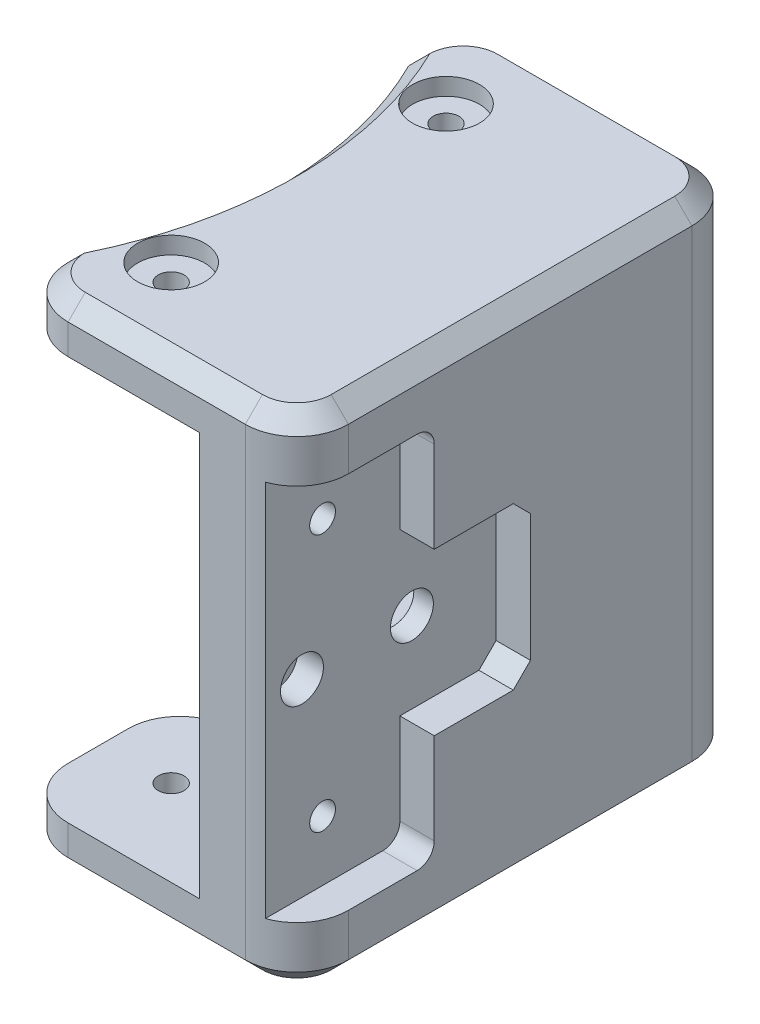
SolidWorks part; units mm, degrees
ref_plane "Спереди" through (0, 0, 0) normal (0, 0, 1) x (1, 0, 0)
ref_plane "Сверху" through (0, 0, 0) normal (0, 1, 0) x (1, 0, 0)
ref_plane "Справа" through (0, 0, 0) normal (1, 0, 0) x (0, 0, -1)
sketch "Эскиз1" plane through (0, 0, 0) normal (0, 1, 0) x (1, 0, 0)
  line L0 (0, 0) -> (25, 0) construction
  line L1 (19.6854, 13) -> (36, 13)
  line L2 (19.6854, 13) -> (19.6854, -13)
  line L3 (19.6854, -13) -> (36, -13)
  line L4 (36, 13) -> (36, -13)
  line L5 (19.6854, 13) -> (36, -13) construction
  line L6 (19.6854, -13) -> (36, 13) construction
  line L7 (23.6854, 8) -> (23.6854, -8) construction
  circle A0 centre (0, 0) radius 25 construction
  circle A1 centre (23.6854, -8) radius 0.75
  circle A2 centre (23.6854, 8) radius 0.75
  point P0 (27.8427, 0)
  dimension "D2" = 50
  dimension "D6" = 1.5
  dimension "D7" = 1.5
  dimension "D1" = 36
  dimension "D3" = 26
  dimension "D4" = 16
  dimension "D5" = 4
extrude "Бобышка-Вытянуть1" add sketch "Эскиз1" along normal mid plane 29
sketch "Эскиз2" plane through (0, 0, 0) normal (0, 1, 0) x (1, 0, 0)
  circle A0 centre (0, 0) radius 33
  dimension "D1" = 66
extrude "Вырез-Вытянуть1" cut sketch "Эскиз2" against normal mid plane 23.5
sketch "Эскиз3" plane through (36, 0, 0) normal (1, 0, 0) x (0, 0, -1)
  line L0 (-13, 11) -> (-5, 11)
  line L1 (-13, 14.5) -> (-13, -14.5) construction
  line L2 (-5, 11) -> (-5, 4.7)
  line L3 (-5, 4.7) -> (0.6, 4.7)
  line L4 (0.6, 4.7) -> (0.6, -4.7)
  line L5 (-13, 11) -> (-13, -11)
  line L6 (0.6, 0) -> (-13, 0) construction
  line L7 (-5, -4.7) -> (0.6, -4.7)
  line L8 (-5, -11) -> (-5, -4.7)
  line L9 (-13, -11) -> (-5, -11)
  dimension "D1" = 8
  dimension "D2" = 13.6
  dimension "D3" = 22
  dimension "D4" = 9.4
extrude "Вырез-Вытянуть2" cut sketch "Эскиз3" against normal blind 2
sketch "Эскиз8" plane through (0, 14.5, 0) normal (0, 1, 0) x (1, 0, 0)
  circle A0 centre (0, 0) radius 22
  dimension "D1" = 44
extrude "Вырез-Вытянуть7" cut sketch "Эскиз8" against normal up to next
fillet "Скругление1" radius 1 2 edges at (35, -11, 5) (35, 11, 5)
chamfer "Фаска1" distance 1 angle 45 2 edges at (35, -4.7, -0.6) (35, 4.7, -0.6)
sketch "Эскиз4" plane through (34, 0, 0) normal (1, 0, 0) x (0, 0, -1)
  line L0 (-13, 11) -> (-13, -11) construction
  circle A0 centre (-4.3, 0) radius 1.25
  circle A1 centre (-10.7, 0) radius 1.25
  dimension "D1" = 2.5
  dimension "D2" = 2.5
  dimension "D3" = 8.7
  dimension "D4" = 6.4
extrude "Вырез-Вытянуть3" cut sketch "Эскиз4" against normal blind 1.5
sketch "Эскиз5" plane through (34, 0, 0) normal (1, 0, 0) x (0, 0, -1)
  line L0 (-13, 0) -> (0, 0) construction
  line L1 (-13, 11) -> (-13, -11) construction
  circle A0 centre (-9.5, 7.5) radius 0.75
  circle A1 centre (-9.5, -7.5) radius 0.75
  dimension "D3" = 1.5
  dimension "D1" = 3.5
  dimension "D2" = 15
extrude "Вырез-Вытянуть4" cut sketch "Эскиз5" against normal through all
sketch "Эскиз6" plane through (0, -14.5, 0) normal (0, -1, 0) x (1, 0, 0)
  line L0 (19.6854, -13) -> (19.6854, 13) construction
  line L1 (25, 3.5) -> (19.6854, 3.5)
  line L2 (25, 3.5) -> (25, -3.5)
  line L3 (25, -3.5) -> (19.6854, -3.5)
  line L4 (19.6854, 3.5) -> (19.6854, -3.5)
  circle A0 centre (0, 0) radius 25 construction
  circle A1 centre (25, 0) radius 3.5
  line M7 (19.6854, 13) -> (19.6854, -13)
  dimension "D1" = 50
  dimension "D2" = 7
extrude "Вырез-Вытянуть5" cut sketch "Эскиз6" against normal up to next contours A1 L1 L3 M7 | L2 A1 | L2 A1 region at (21.0872, -14.5, 0) region at (26.4854, -14.5, 0) region at (23.5146, -14.5, 0)
fillet "Скругление2" radius 3 8 edges at (19.6854, 13.125, -13) (19.6854, 13.125, 13) (19.6854, -13.125, -13) (19.6854, -13.125, 13) (36, 0, -13) (36, 12.75, 13) (19.6854, -13.125, 3.5) (19.6854, -13.125, -3.5)
chamfer "Фаска3" distance 1 angle 45 22 edges at (23.8427, -14.5, 3.5) (28.5, -14.5, 0) (20.5641, -14.5, 4.3787) (23.8427, -14.5, -3.5) (19.6854, -14.5, 8.25) (20.5641, -14.5, -4.3787) (20.5641, -14.5, 12.1213) (19.6854, -14.5, -8.25) (27.8427, -14.5, 13) (20.5641, -14.5, -12.1213) (35.1213, -14.5, 12.1213) (27.8427, -14.5, -13) (36, -14.5, 0) (35.1213, -14.5, -12.1213) (27.8427, 14.5, 13) (35.1213, 14.5, 12.1213) (20.5641, 14.5, 12.1213) (36, 14.5, 0) (35.1213, 14.5, -12.1213) (20.5641, 14.5, -12.1213) (27.8427, 14.5, -13) (19.6854, 14.5, 9.9113)
sketch "Эскиз7" plane through (0, 14.5, 0) normal (0, 1, 0) x (1, 0, 0)
  circle A0 centre (23.6854, 8) radius 1.95
  circle A1 centre (23.6854, -8) radius 1.95
  dimension "D1" = 3.9
  dimension "D2" = 3.9
extrude "Вырез-Вытянуть6" cut sketch "Эскиз7" against normal blind 1
mirror "Зеркальное отражение1" about plane through (0, 0, 0) normal (0, 1, 0) of "Вырез-Вытянуть6"
chamfer "Фаска4" distance 1 angle 45 1 edges at (22, 14.5, 0)
equation "\"motor_diameter\"= 30"
equation "\"mm_diameter\"= IIF ( \"motor_diameter\" < 34 , 41 , \"motor_diameter\" + 8 )"
equation "\"upper_shafts_diameter\"= 5"
equation "\"upper_shats_length\"= 180"
equation "\"upper_bearing_d1\"= 10"
equation "\"upper_bearing_d2\"= 5"
equation "\"upper_bearing_h\"= 15"
equation "\"lower_shafts_diameter\"= 5"
equation "\"lower_shafts_length\"= 180"
equation "\"lower_bearing_d1\"= 10"
equation "\"lower_bearing_d2\"= 5"
equation "\"lower_bearing_h\"= 15"
equation "\"print_offset\"= 0.5"
equation "\"bh_screws_d\"= 2"
equation "\"bh_screws_h\"= 20"
equation "\"bh_screws_hh_d\"= 3.4"
equation "\"bh_screws_hh_h\"= 2"
equation "\"bh_nut_d\"= 3.8"
equation "\"bh_nut_h\"= 2"
equation "\"motor_screws_d\"= 3"
equation "\"motor_screws_h\"= 16"
equation "\"motor_screws_hh_d\"= 5.5"
equation "\"motor_screws_hh_h\"= 3"
equation "\"plate_hole_distance\"= 25.4"
equation "\"plate_screws_d\"= 6.5"
equation "\"shafts_diameter\"= IIF ( \"mm_diameter\" < 42 , 42 + 8 , \"mm_diameter\" + 8 )"
equation "\"central_hole_diameter\"= 8"
equation "\"bh_thikness\"= 4"
equation "\"ends_screws_d\"= 4"
equation "\"ends_screws_h\"= 16"
equation "\"ends_screws_hh_d\"= 6.7"
equation "\"ends_screws_hh_h\"= 4.1"
equation "\"ends_nut_d\"= 6.8"
equation "\"ends_nut_h\"= 3"
equation "\"system_radius\" = ( \"shafts_diameter\" + 12 + \"bh_thikness\" / 2 ) / 2"
equation "\"encoder_distance\"= \"system_radius\" + 4"
equation "\"tape_position\"= \"encoder_distance\" - 2 + 3.9 + 1.7 / 2"
equation "\"D1@Эскиз1\"=\"encoder_distance\""
equation "\"D2@Эскиз1\"=\"shafts_diameter\""
equation "\"D5@Эскиз1\"=\"bh_thikness\""
equation "\"D6@Эскиз1\"=\"bh_screws_d\"-\"print_offset\""
equation "\"D7@Эскиз1\"=\"D6@Эскиз1\""
equation "\"D1@Бобышка-Вытянуть1\"=\"upper_bearing_h\"+\"bh_thikness\"*2+3*2"
equation "\"D1@Эскиз2\"=\"system_radius\"*2+2"
equation "\"D1@Вырез-Вытянуть1\"=\"upper_bearing_h\"+\"bh_thikness\"*2+\"print_offset\""
equation "\"D1@Эскиз3\"=\"print_offset\"*2+7"
equation "\"D2@Эскиз3\"=\"print_offset\"*2+12.6"
equation "\"D3@Эскиз3\"=\"print_offset\"*2+21"
equation "\"D4@Эскиз3\"=\"print_offset\"*2+8.4"
equation "\"D2@Эскиз4\"=\"print_offset\"+2"
equation "\"D1@Эскиз4\"=\"D2@Эскиз4\""
equation "\"D1@Эскиз5\"=7/2"
equation "\"D3@Эскиз5\"=\"bh_screws_d\"-\"print_offset\""
equation "\"D1@Эскиз6\"=\"shafts_diameter\""
equation "\"D2@Эскиз6\"=\"lower_shafts_diameter\"+2"
equation "\"D1@Эскиз7\"=\"bh_screws_hh_d\"+\"print_offset\""
equation "\"D2@Эскиз7\"=\"D1@Эскиз7\""
equation "\"D1@Эскиз8\"= IIF ( \"mm_diameter\" < 42 , 44 , \"mm_diameter\" + 2 )"
